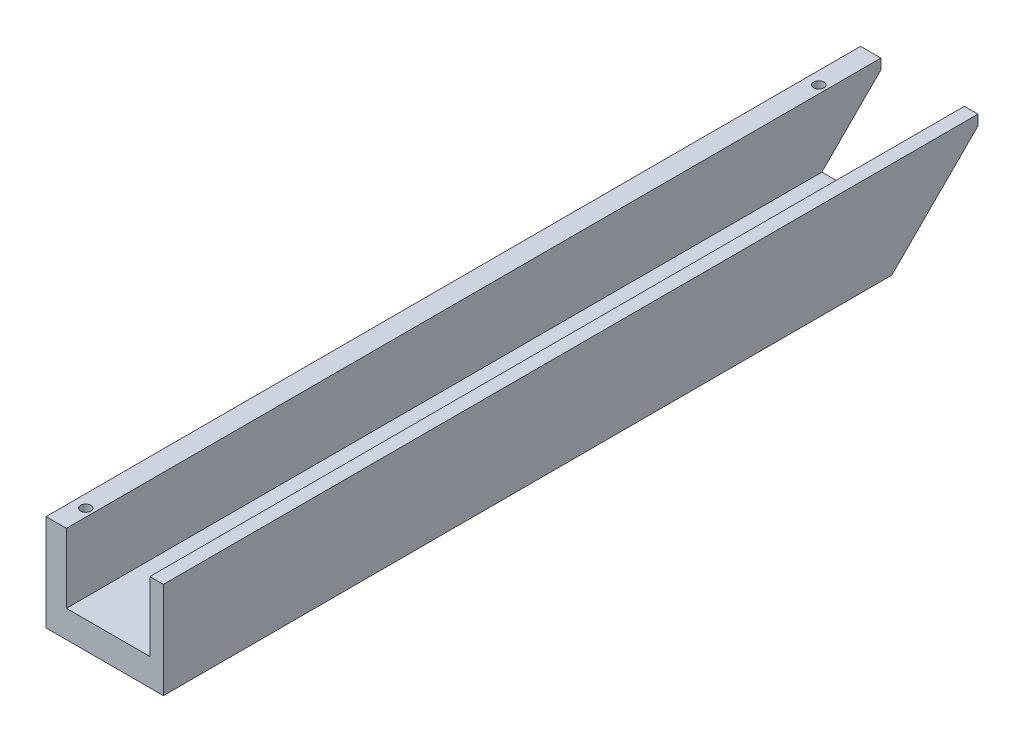
SolidWorks part; units mm, degrees
ref_plane "Front Plane" through (0, 0, 0) normal (0, 0, 1) x (1, 0, 0)
ref_plane "Top Plane" through (0, 0, 0) normal (0, 1, 0) x (1, 0, 0)
ref_plane "Right Plane" through (0, 0, 0) normal (1, 0, 0) x (0, 0, -1)
ref_axis "X-Axis" through (0, 0, 0) along (1, 0, 0)
ref_axis "Y-Axis" through (0, 42.2917, 0) along (0, -1, 0)
ref_axis "Z-Axis" through (0, 0, 55.0015) along (0, 0, -1)
sketch "Sketch1" plane through (0, 0, 0) normal (0, 0, 1) x (1, 0, 0)
  line L0 (-0.0089, 6.7786) -> (2.9911, 6.7786)
  line L1 (2.9911, 6.7786) -> (2.9911, -3.4214)
  line L2 (2.9911, -3.4214) -> (15.2911, -3.4214)
  line L3 (15.2911, -3.4214) -> (15.2911, 6.7786)
  line L4 (15.2911, 6.7786) -> (17.2911, 6.7786)
  line L5 (17.2911, 6.7786) -> (17.2911, -7.4214)
  line L6 (17.2911, -7.4214) -> (-0.0089, -7.4214)
  line L7 (-0.0089, -7.4214) -> (-0.0089, 6.7786)
  line L8 (-0.8459, -4.4214) -> (52.4677, -4.4214) construction
  line L9 (52.4677, -4.4214) -> (52.4677, 5.5786) construction
  line L10 (52.4677, 5.5786) -> (-1.8799, 5.5786) construction
  dimension "D1" = 3
  dimension "D2" = 2
  dimension "D3" = 12.3
  dimension "D4" = 4
  dimension "D5" = 14.2
  dimension "Largeur_Rail" = 17.3
  dimension "Profondeur_Rail" = 10.2
extrude "Rail-Extrude" add sketch "Sketch1" along normal blind 120
sketch "Sketch2" plane through (0, 6.7786, 0) normal (0, 1, 0) x (1, 0, 0)
  line L0 (1.8411, 0) -> (1.8411, -8) construction
  line L1 (2.9911, 0) -> (-0.0089, 0) construction
  line L2 (-0.0089, -120) -> (-0.0089, 0) construction
  circle A0 centre (1.8411, -8) radius 0.75
  dimension "D1" = 1.5
  dimension "D2" = 8
  dimension "D3" = 1.85
extrude "First Hole" cut sketch "Sketch2" against normal through all
sketch "Sketch3" plane through (0, 6.7786, 0) normal (0, 1, 0) x (1, 0, 0)
  line L0 (1.8411, -8) -> (1.8411, -116) construction
  circle A0 centre (1.8411, -116) radius 0.75
  circle A1 centre (1.8411, -8) radius 0.75 construction
  dimension "D1" = 108
extrude "Last Hole" cut sketch "Sketch3" against normal through all
sketch "Sketch5" plane through (-0.0089, 0, 0) normal (-1, 0, 0) x (0, 0, 1)
  line L5 (120, 6.7786) -> (0, 6.7786) construction
  line L6 (120, -7.4214) -> (0, -7.4214) construction
  line L7 (0, -5.4214) -> (10, -5.4214) construction
  line L8 (0, -5.4214) -> (0, -7.4214) construction
  line L9 (0, -7.4214) -> (10, -7.4214) construction
  line L10 (10, -5.4214) -> (10, -7.4214) construction
  line L11 (0, 6.7786) -> (0, -7.4214) construction
  line L12 (12.7, -7.4214) -> (0, 5.2786)
  line L13 (0, 5.2786) -> (0, -7.4214)
  line L14 (0, -7.4214) -> (12.7, -7.4214)
  dimension "D1" = 2
  dimension "D2" = 10
  dimension "D3" = 45
  dimension "D4" = 1.5
extrude "Angle" cut sketch "Sketch5" against normal through all
equation "\"Largeur Bande\"= 16.3"
equation "\"Largeur_Rail\"= \"Largeur Bande\" + 1"
equation "\"Profondeur Bande\"= 10"
equation "\"Profondeur_Rail\" = \"Profondeur Bande\" + 0.2"
equation "\"Largeur Feeder\"= \"Largeur Rail\" + 1.2 + 1.2 + 0.3"
equation "\"Largeur Rail\"= \"Largeur Bande\" + 1"
equation "\"D1@Boss-Extrude1\"=\"Largeur Feeder\"/2"
equation "\"D2@Boss-Extrude1\"=\"Largeur Feeder\"/2"
